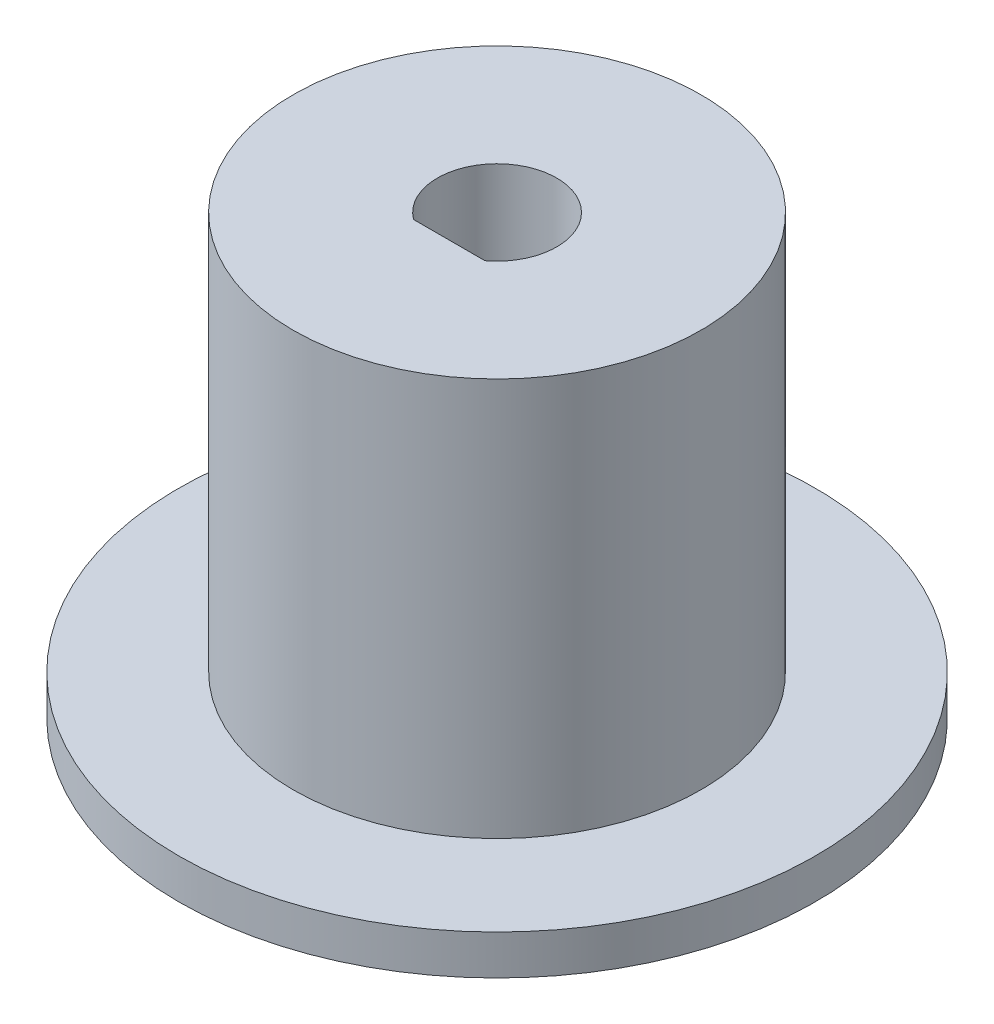
SolidWorks part; units mm, degrees
ref_plane "Front Plane" through (0, 0, 0) normal (0, 0, 1) x (1, 0, 0)
ref_plane "Top Plane" through (0, 0, 0) normal (0, 1, 0) x (1, 0, 0)
ref_plane "Right Plane" through (0, 0, 0) normal (1, 0, 0) x (0, 0, -1)
sketch "Sketch1" plane through (0, 0, 0) normal (0, 1, 0) x (1, 0, 0)
  circle A0 centre (0, 0) radius 16
  dimension "D1" = 32
extrude "Boss-Extrude1" add sketch "Sketch1" along normal blind 2
sketch "Sketch2" plane through (0, 2, 0) normal (0, 1, 0) x (1, 0, 0)
  circle A0 centre (0, 0) radius 10.25
  dimension "D1" = 20.5
extrude "Boss-Extrude2" add sketch "Sketch2" along normal blind 20
sketch "Sketch3" plane through (0, 0, 0) normal (0, -1, 0) x (1, 0, 0)
  line L0 (0, -3) -> (0, 2.4045)
  line L1 (0, 2.4045) -> (-1.794, 2.4045)
  line L2 (0, 2.4045) -> (1.794, 2.4045)
  circle A0 centre (0, 0) radius 3
extrude "Cut-Extrude1" cut sketch "Sketch3" against normal through all contours L0 A0 L2 | L1 A0 L0 region at (-1.3053, 0, -0.1435) region at (1.3053, 0, -0.1435)
